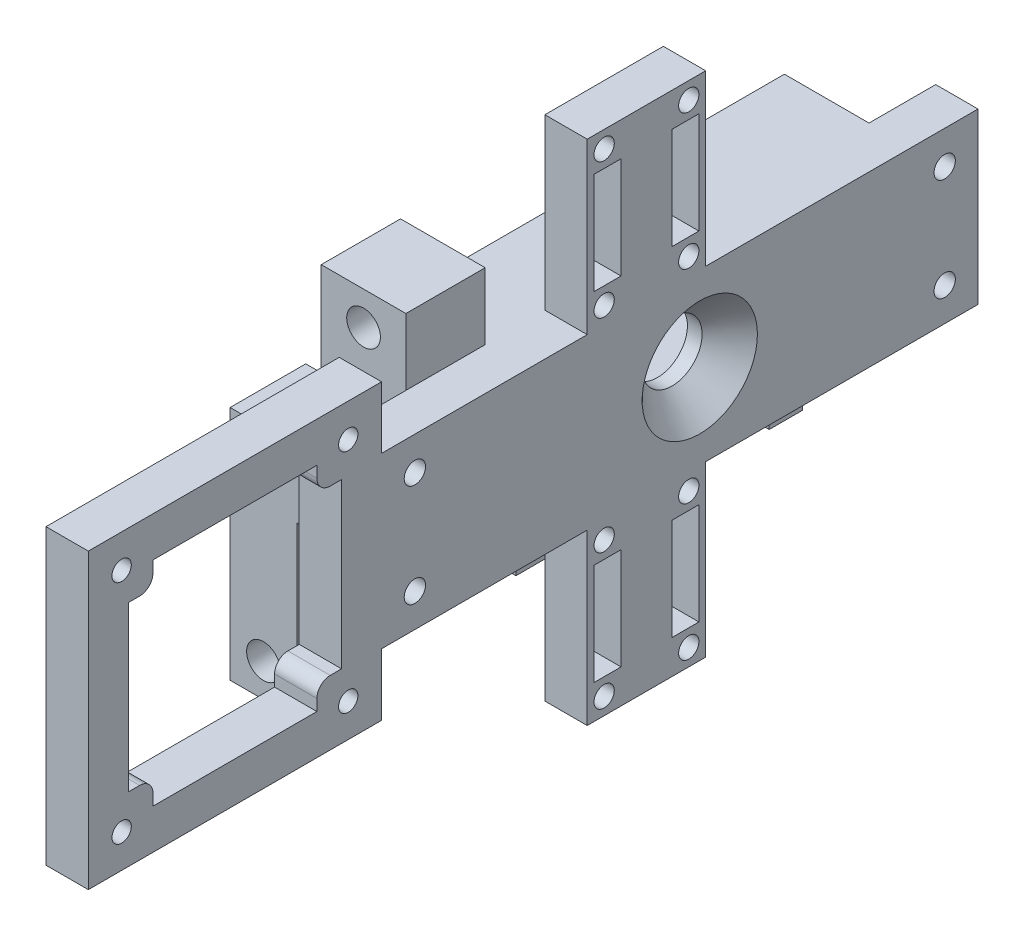
SolidWorks part; units mm, degrees
ref_plane "Front Plane" through (0, 0, 0) normal (0, 0, 1) x (1, 0, 0)
ref_plane "Top Plane" through (0, 0, 0) normal (0, 1, 0) x (1, 0, 0)
ref_plane "Right Plane" through (0, 0, 0) normal (1, 0, 0) x (0, 0, -1)
sketch "Sketch1" plane through (0, 0, 0) normal (0, 1, 0) x (1, 0, 0)
  line L1 (0, 0) -> (6.35, 0)
  line L2 (0, 0) -> (0, 89.5)
  line L3 (0, 89.5) -> (6.35, 89.5)
  line L4 (6.35, 0) -> (6.35, 89.5)
  dimension "D1" = 89.5
  dimension "D2" = 6.35
extrude "Boss-Extrude1" add sketch "Sketch1" along normal blind 25.4
sketch "Sketch2" plane through (0, 0, 0) normal (-1, 0, 0) x (0, 0, 1)
  line L0 (-89.5, 25.4) -> (0, 25.4) construction
  line L1 (-74.15, 20.05) -> (-21.35, 20.05)
  line L2 (-74.15, 20.05) -> (-74.15, 5.35)
  line L3 (-74.15, 5.35) -> (-21.35, 5.35)
  line L4 (-21.35, 20.05) -> (-21.35, 5.35)
  line L6 (-89.5, 25.4) -> (-89.5, 0) construction
  line L13 (-89.5, 0) -> (0, 0) construction
  line L14 (-79.5, 25.4) -> (-10, 25.4)
  line L15 (-79.5, 25.4) -> (-79.5, 0)
  line L16 (-79.5, 0) -> (-10, 0)
  line L17 (-10, 25.4) -> (-10, 0)
  line L18 (0, 25.4) -> (0, 0) construction
  dimension "D1" = 52.8
  dimension "D2" = 14.7
  dimension "D3" = 5.35
  dimension "D4" = 15.35
  dimension "D5" = 10
  dimension "D6" = 10
sketch "Sketch4" plane through (6.35, 0, 0) normal (1, 0, 0) x (0, 0, -1)
  line L0 (0, 25.4) -> (0, 0) construction
  line L1 (0, 34.7) -> (-44, 34.7)
  line L2 (0, 34.7) -> (0, -9.3)
  line L3 (0, -9.3) -> (-44, -9.3)
  line L4 (-44, 34.7) -> (-44, -9.3)
  line L6 (0, 25.4) -> (89.5, 25.4) construction
  circle A0 centre (-39, 29.7) radius 1.45
  circle A1 centre (-5, 29.7) radius 1.45
  circle A2 centre (-39, -4.3) radius 1.45
  circle A3 centre (-5, -4.3) radius 1.45
  dimension "D4" = 34
  dimension "D6" = 2.9
  dimension "D7" = 34
  dimension "D1" = 44
  dimension "D2" = 9.3
  dimension "D3" = 44
  dimension "D5" = 5
  dimension "D8" = 5
extrude "Boss-Extrude2" add sketch "Sketch4" against normal up to surface (6.35 mm away) up to face at (0, 12.7, -44.75)
hole_wizard "CSK for M8 Flat Head Machine Screw1" positions "Sketch6" profile "Sketch7" countersink size "M8" standard "ANSI Metric"
sketch "Sketch6" plane through (6.35, 0, 0) normal (1, 0, 0) x (0, 0, -1)
  line L1 (89.5, 25.4) -> (89.5, 0) construction
  line L2 (0, 25.4) -> (89.5, 25.4) construction
  point P0 (47.75, 12.7)
  dimension "D1" = 41.75
  dimension "D2" = 12.7
sketch "Sketch7" plane through (6.35, 12.7, -47.75) normal (0, 1, 0) x (0, 0, -1)
  line L0 (0, 0) -> (0, 20.2039)
  line L1 (0, 20.2039) -> (4.5, 17.5)
  line L2 (4.5, 17.5) -> (4.5, 4.15)
  line L3 (4.5, 4.15) -> (8.65, 0)
  line L5 (8.65, 0) -> (0, 0)
  line L6 (-4.5, 4.15) -> (-8.65, 0) construction
  line L10 (0, 20.2039) -> (-4.5, 17.5) construction
  line L11 (0, -6.35) -> (0, 107.95) construction
  dimension "Hole Dia." = 9
  dimension "Hole Depth" = 17.5
  dimension "Near C'Sink Dia." = 17.3
  dimension "Near C'Sink Angle" = 90
  dimension "Drill Angle" = 118
extrude "Boss-Extrude3" add sketch "Sketch2" along normal blind 12.7
sketch "Sketch9" plane through (0, 0, 0) normal (-1, 0, 0) x (0, 0, 1)
  line L1 (0, 34.7) -> (0, 25.4) construction
  line L2 (-10, 25.4) -> (0, 25.4) construction
  line L3 (-10, 0) -> (0, 0) construction
  line L4 (-89.5, 25.4) -> (-89.5, 0) construction
  circle A0 centre (-5, 20.4) radius 1.6
  circle A1 centre (-5, 5) radius 1.6
  circle A3 centre (-84.5, 5) radius 1.6
  circle A4 centre (-84.5, 20.4) radius 1.6
  dimension "D1" = 3.2
  dimension "D2" = 5
  dimension "D3" = 5
  dimension "D4" = 5
  dimension "D5" = 5
extrude "Cut-Extrude1" cut sketch "Sketch9" against normal up to surface (6.35 mm away) up to face at (6.35, 12.7, -56.4)
sketch "Sketch10" plane through (6.35, 0, 0) normal (1, 0, 0) x (0, 0, -1)
  line L0 (0, 25.4) -> (89.5, 25.4) construction
  line L1 (30.86, 25.4) -> (48.64, 25.4)
  line L2 (30.86, 25.4) -> (30.86, 50.8)
  line L3 (30.86, 50.8) -> (48.64, 50.8)
  line L4 (48.64, 25.4) -> (48.64, 50.8)
  line L6 (0, 25.4) -> (0, 34.7) construction
  line L7 (0, 0) -> (89.5, 0) construction
  line L8 (30.86, 0) -> (48.64, 0)
  line L9 (30.86, 0) -> (30.86, -25.4)
  line L10 (30.86, -25.4) -> (48.64, -25.4)
  line L11 (48.64, 0) -> (48.64, -25.4)
  circle A0 centre (33.4, 27.94) radius 1.524
  circle A1 centre (46.1, 27.94) radius 1.524
  circle A2 centre (46.1, 48.26) radius 1.524
  circle A3 centre (33.4, 48.26) radius 1.524
  circle A4 centre (33.4, -2.54) radius 1.524
  circle A5 centre (46.1, -2.54) radius 1.524
  circle A6 centre (33.4, -22.86) radius 1.524
  circle A7 centre (46.1, -22.86) radius 1.524
  dimension "D3" = 3.048
  dimension "D11" = 2.54
  dimension "D1" = 25.4
  dimension "D2" = 17.78
  dimension "D4" = 20.32
  dimension "D5" = 12.7
  dimension "D6" = 2.54
  dimension "D7" = 2.54
  dimension "D8" = 30.86
  dimension "D9" = 25.4
  dimension "D10" = 17.78
  dimension "D12" = 20.32
extrude "Boss-Extrude4" add sketch "Sketch10" against normal blind 6.35
sketch "Sketch11" plane through (6.35, 0, 0) normal (1, 0, 0) x (0, 0, -1)
  line L0 (0, 0) -> (30.86, 0) construction
  line L1 (31.876, -5.08) -> (35.94, -5.08)
  line L2 (31.876, -5.08) -> (31.876, -20.32)
  line L3 (31.876, -20.32) -> (35.94, -20.32)
  line L4 (35.94, -5.08) -> (35.94, -20.32)
  line L5 (43.56, -5.08) -> (47.624, -5.08)
  line L6 (43.56, -5.08) -> (43.56, -20.32)
  line L7 (43.56, -20.32) -> (47.624, -20.32)
  line L8 (47.624, -5.08) -> (47.624, -20.32)
  line L9 (30.86, -25.4) -> (48.64, -25.4) construction
  line L10 (30.86, 0) -> (30.86, -25.4) construction
  line L11 (48.64, -25.4) -> (48.64, 0) construction
  line L12 (48.64, 50.8) -> (30.86, 50.8) construction
  line L13 (31.876, 45.72) -> (35.94, 45.72)
  line L14 (31.876, 45.72) -> (31.876, 30.48)
  line L15 (31.876, 30.48) -> (35.94, 30.48)
  line L16 (35.94, 45.72) -> (35.94, 30.48)
  line L17 (43.56, 45.72) -> (47.624, 45.72)
  line L18 (43.56, 45.72) -> (43.56, 30.48)
  line L19 (43.56, 30.48) -> (47.624, 30.48)
  line L20 (47.624, 45.72) -> (47.624, 30.48)
  line L21 (0, 25.4) -> (30.86, 25.4) construction
  dimension "D1" = 5.08
  dimension "D2" = 5.08
  dimension "D3" = 1.016
  dimension "D4" = 4.064
  dimension "D5" = 1.016
  dimension "D6" = 5.08
  dimension "D7" = 5.08
extrude "Cut-Extrude2" cut sketch "Sketch11" against normal up to surface (6.35 mm away) up to face at (0, -22.86, -47.624)
sketch "Sketch14" plane through (0, 25.4, 0) normal (0, 1, 0) x (1, 0, 0)
  line L0 (-12.7, 10) -> (-12.7, 79.5) construction
  line L1 (0, 10) -> (-12.7, 10)
  line L2 (0, 10) -> (0, 21.9)
  line L3 (0, 21.9) -> (-12.7, 21.9)
  line L4 (-12.7, 10) -> (-12.7, 21.9)
  dimension "D1" = 11.9
extrude "Boss-Extrude5" add sketch "Sketch14" along normal blind 10
sketch "Sketch15" plane through (0, 0, -10) normal (0, 0, 1) x (1, 0, 0)
  line L0 (-12.7, 0) -> (-12.7, 35.4) construction
  line L1 (-12.7, 35.4) -> (0, 35.4) construction
  circle A0 centre (-6.35, 30.4) radius 2.5273
  dimension "D1" = 6.35
  dimension "D2" = 5.0546
  dimension "D3" = 5
extrude "Cut-Extrude4" cut sketch "Sketch15" against normal blind 7
sketch "Sketch16" plane through (-12.7, 0, 0) normal (-1, 0, 0) x (0, 0, 1)
  line L0 (-10, 0) -> (-10, 35.4) construction
  line L1 (-10, 10) -> (-21.35, 10)
  line L2 (-10, 10) -> (-10, 0)
  line L3 (-10, 0) -> (-21.35, 0)
  line L4 (-21.35, 10) -> (-21.35, 0)
  line L5 (-79.5, 0) -> (-10, 0) construction
  dimension "D1" = 10
  dimension "D2" = 11.35
extrude "Boss-Extrude6" add sketch "Sketch16" along normal blind 13.6718
sketch "Sketch17" plane through (0, 0, 0) normal (0, -1, 0) x (1, 0, 0)
  line L0 (-26.3718, -21.35) -> (-12.7, -21.35) construction
  line L1 (-26.3718, -10) -> (-16.3718, -10)
  line L2 (-26.3718, -10) -> (-26.3718, -21.35)
  line L3 (-26.3718, -21.35) -> (-16.3718, -21.35)
  line L4 (-16.3718, -10) -> (-16.3718, -21.35)
  dimension "D1" = 10
extrude "Boss-Extrude7" add sketch "Sketch17" along normal blind 25.4523
sketch "Sketch18" plane through (0, 0, -10) normal (0, 0, 1) x (1, 0, 0)
  line L0 (-16.3718, -25.4523) -> (-26.3718, -25.4523) construction
  line L1 (-26.3718, -25.4523) -> (-26.3718, 10) construction
  circle A0 centre (-21.3718, -20.4523) radius 2.5273
  circle A1 centre (-6.35, 30.4) radius 2.5273 construction
  dimension "D1" = 5
  dimension "D2" = 5
extrude "Cut-Extrude5" cut sketch "Sketch18" against normal blind 7
sketch "Sketch19" plane through (0, 0, 0) normal (0, -1, 0) x (1, 0, 0)
  line L0 (-12.7, -79.5) -> (-12.7, -21.35) construction
  line L1 (-12.7, -47.925) -> (-18.0384, -47.925)
  line L2 (-12.7, -47.925) -> (-12.7, -57.925)
  line L3 (-12.7, -57.925) -> (-18.0384, -57.925)
  line L4 (-18.0384, -47.925) -> (-18.0384, -57.925)
  line L5 (-16.3718, -21.35) -> (-12.7, -21.35) construction
  dimension "D1" = 10
  dimension "D2" = 26.575
  dimension "D3" = 5.3384
extrude "Boss-Extrude8" add sketch "Sketch19" against normal up to surface (5.35 mm away) up to face at (-6.35, 5.35, -47.75)
sketch "Sketch21" plane through (0, 0, 0) normal (0, -1, 0) x (1, 0, 0)
  line L0 (-12.7, -47.925) -> (-12.7, -21.35) construction
  line L1 (-18.0384, -47.925) -> (-12.7, -47.925)
  line L2 (-18.0384, -47.925) -> (-18.0384, -57.925)
  line L3 (-18.0384, -57.925) -> (-12.7, -57.925)
  line L4 (-12.7, -47.925) -> (-12.7, -57.925)
  line L5 (-12.7, -31.425) -> (-4.9108, -31.425)
  line L6 (-12.7, -31.425) -> (-12.7, -36.425)
  line L7 (-12.7, -36.425) -> (-4.9108, -36.425)
  line L8 (-4.9108, -31.425) -> (-4.9108, -36.425)
  line L9 (-12.7, -79.5) -> (-12.7, -57.925) construction
  line L10 (-12.7, -69.425) -> (-4.9108, -69.425)
  line L11 (-12.7, -69.425) -> (-12.7, -74.425)
  line L12 (-12.7, -74.425) -> (-4.9108, -74.425)
  line L13 (-4.9108, -69.425) -> (-4.9108, -74.425)
  point P12 (-12.7, -52.925)
  point P19 (-15.3692, -47.925)
  dimension "D1" = 21.5
  dimension "D2" = 10.4584
  dimension "D3" = 5
  dimension "D4" = 43
  dimension "D5" = 5
extrude "Boss-Extrude9" add sketch "Sketch21" along normal blind 11.85
sketch "Sketch22" plane through (0, -11.85, 0) normal (0, -1, 0) x (1, 0, 0)
  line L0 (-12.7, -47.925) -> (-18.0384, -47.925) construction
  line L1 (-18.0384, -47.925) -> (-18.0384, -57.925) construction
  circle A0 centre (-12.5308, -52.925) radius 2.5273
  dimension "D1" = 5
  dimension "D3" = 5.0546
  dimension "D2" = 5.5076
sketch "Sketch23" plane through (-12.7, 0, 0) normal (1, 0, 0) x (0, 0, -1)
  line L1 (47.925, 0) -> (57.925, 0)
  line L2 (47.925, 0) -> (47.925, -11.85)
  line L3 (47.925, -11.85) -> (57.925, -11.85)
  line L4 (57.925, 0) -> (57.925, -11.85)
extrude "Boss-Extrude10" add sketch "Sketch23" along normal blind 4.6616
extrude "Cut-Extrude6" cut sketch "Sketch22" against normal blind 7
sketch "Sketch25" plane through (-18.0384, 0, 0) normal (-1, 0, 0) x (0, 0, 1)
  line L5 (-47.925, 5.35) -> (-47.925, -11.85) construction
  line L6 (-57.925, 5.35) -> (-47.925, 5.35)
  line L7 (-57.925, 5.35) -> (-57.925, 0)
  line L8 (-57.925, 0) -> (-47.925, 0)
  line L9 (-47.925, 5.35) -> (-47.925, 0)
  line L10 (-48.64, 0) -> (-30.86, 0) construction
extrude "Cut-Extrude7" cut sketch "Sketch25" against normal up to surface (5.3384 mm away) up to face at (-12.7, 10.5437, -51.0844)
sketch "Sketch26" plane through (6.35, 0, 0) normal (1, 0, 0) x (0, 0, -1)
  line L23 (-34.3, 28.7) -> (-9.7, 28.7)
  line L26 (-38, 25) -> (-38, 0.4)
  line L27 (-34.3, -3.3) -> (-9.7, -3.3)
  line L28 (-6, 25) -> (-6, 0.4)
  line L30 (-44, 34.7) -> (-44, -9.3) construction
  line L31 (-44, -9.3) -> (0, -9.3) construction
  line L33 (-34.3, 28.7) -> (-34.3, 25)
  line L34 (-38, 25) -> (-34.3, 25)
  line L35 (-9.7, 28.7) -> (-9.7, 25)
  line L36 (-9.7, 25) -> (-6, 25)
  line L37 (-6, 0.4) -> (-9.7, 0.4)
  line L38 (-9.7, 0.4) -> (-9.7, -3.3)
  line L39 (-38, 0.4) -> (-34.3, 0.4)
  line L40 (-34.3, 0.4) -> (-34.3, -3.3)
  line L41 (0, 25.4) -> (0, 34.7) construction
  line L42 (0, 34.7) -> (-44, 34.7) construction
  dimension "D5" = 3.7
  dimension "D6" = 3.7
  dimension "D9" = 3.7
  dimension "D11" = 3.7
  dimension "D7" = 6
  dimension "D2" = 3.7
  dimension "D3" = 6
  dimension "D4" = 6
  dimension "D8" = 3.7
  dimension "D10" = 3.7
  dimension "D12" = 6
extrude "Cut-Extrude8" cut sketch "Sketch26" against normal up to surface (6.35 mm away) up to face at (0, 5, -3.4)
fillet "Fillet1" radius 2 4 edges at (3.175, 25, 9.7) (3.175, 0.4, 34.3) (3.175, 0.4, 9.7) (3.175, 25, 34.3)
equation "\"D1@Cut-Extrude4\"=4"
